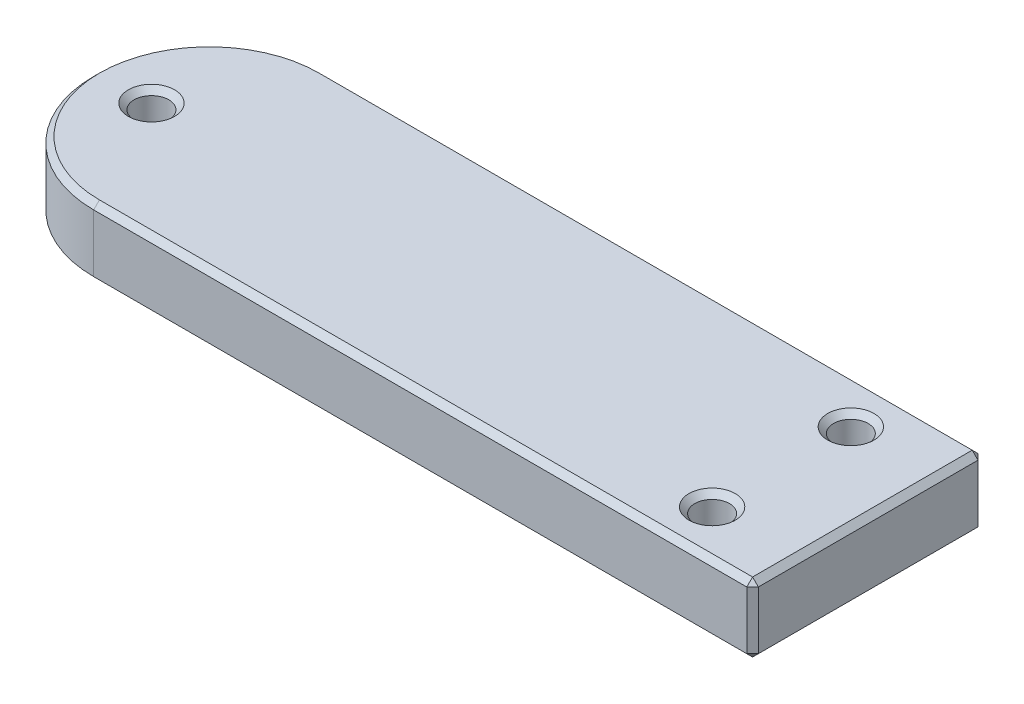
SolidWorks part; units mm, degrees
ref_plane "Alzado" through (0, 0, 0) normal (0, 0, 1) x (1, 0, 0)
ref_plane "Planta" through (0, 0, 0) normal (0, 1, 0) x (1, 0, 0)
ref_plane "Vista lateral" through (0, 0, 0) normal (1, 0, 0) x (0, 0, -1)
sketch "Croquis1" plane through (0, 0, 0) normal (0, 1, 0) x (1, 0, 0)
  line L1 (62, 10) -> (-5, 10)
  line L2 (62, 10) -> (62, -10)
  line L3 (62, -10) -> (-5, -10)
  line L4 (-5, 10) -> (-5, -10)
  circle A0 centre (0, 0) radius 1.5
  circle A1 centre (54.5, 6) radius 1.5
  circle A2 centre (54.5, -6) radius 1.5
  dimension "D1" = 3
  dimension "D2" = 3
  dimension "D3" = 3
  dimension "D4" = 54.5
  dimension "D5" = 10
  dimension "D6" = 12
  dimension "D7" = 6
  dimension "D8" = 20
  dimension "D9" = 5
  dimension "D10" = 7.5
extrude "Saliente-Extruir1" add sketch "Croquis1" along normal blind 6
fillet "Redondeo1" radius 10 2 edges at (-5, 3, -10) (-5, 3, 10)
chamfer "Chaflán2" distance 0.5 angle 45 18 edges at (54.5, 0, 7.5) (0, 0, 1.5) (54.5, 0, -4.5) (54.5, 6, 7.5) (0, 6, 1.5) (62, 3, 10) (33.5, 0, 10) (62, 0, 0) (-2.0711, 0, 7.0711) (-2.0711, 0, -7.0711) (33.5, 0, -10) (62, 3, -10) (62, 6, 0) (33.5, 6, 10) (-2.0711, 6, 7.0711) (-2.0711, 6, -7.0711) (33.5, 6, -10) (54.5, 6, -4.5)
